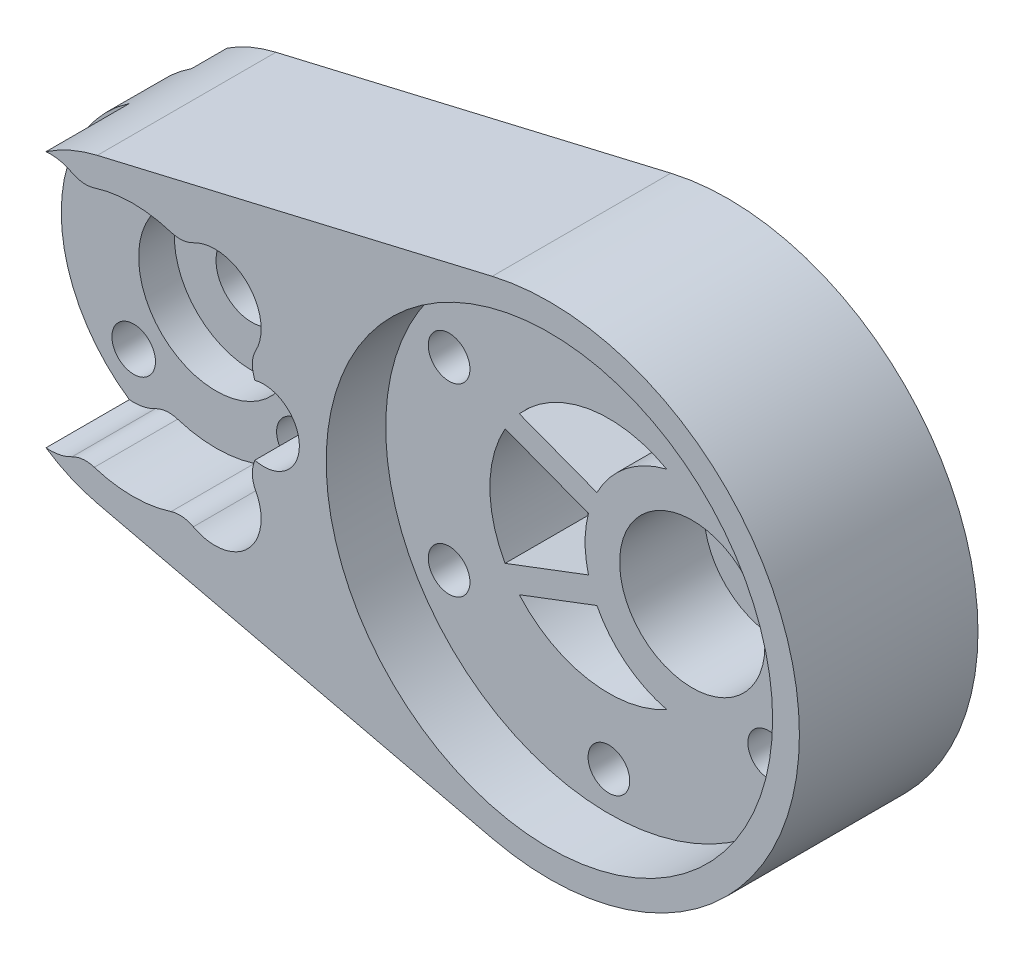
SolidWorks part; units mm, degrees
material "ABS"
ref_plane "Front Plane" through (0, 0, 0) normal (0, 0, 1) x (1, 0, 0)
ref_plane "Top Plane" through (0, 0, 0) normal (0, 1, 0) x (1, 0, 0)
ref_plane "Right Plane" through (0, 0, 0) normal (1, 0, 0) x (0, 0, -1)
sketch "layout" plane through (0, 0, 0) normal (0, 0, 1) x (1, 0, 0)
  line L0 (-87.1613, 0) -> (148.5806, 0) construction
  line L1 (0, 77.4516) -> (0, -79.4839) construction
  line L2 (-2.9714, 12.6559) -> (30.2, 20.4441)
  line L3 (30.2, -20.4441) -> (-2.9714, -12.6559)
  circle A0 centre (0, 0) radius 13
  circle A1 centre (35, 0) radius 21
  circle A3 centre (42, 0) radius 3
  circle A4 centre (11, 0) radius 1.5
  dimension "D1" = 7
  dimension "D2" = 42
  dimension "D3" = 26
  dimension "D4" = 42
  dimension "D5" = 6
  dimension "D6" = 31
  dimension "D7" = 3
sketch "Sketch2" plane through (0, 0, 0) normal (0, 0, 1) x (1, 0, 0)
  line L0 (-2.9714, 12.6559) -> (30.2, 20.4441)
  line L1 (30.2, -20.4441) -> (-2.9714, -12.6559)
  arc A0 (-2.9714, 12.6559) -> (-2.9714, -12.6559) centre (0, 0) ccw
  arc A1 (30.2, -20.4441) -> (30.2, 20.4441) centre (35, 0) ccw
extrude "Boss-Extrude1" add sketch "Sketch2" along normal blind 15
sketch "Sketch5" plane through (0, 0, 15) normal (0, 0, 1) x (1, 0, 0)
  line B0 (2.48, 1.6881) -> (2.48, -1.6881)
  line B1 (-16.002, 0.635) -> (-2.932, 0.635)
  line B2 (-16.002, 4.7625) -> (-16.002, 0.635)
  line B3 (-13.2056, 4.7625) -> (-16.002, 4.7625)
  line B4 (-12.573, -4.7625) -> (-12.573, -4.8306)
  line B5 (-16.002, -4.7625) -> (-12.573, -4.7625)
  line B6 (-16.002, -0.635) -> (-16.002, -4.7625)
  line B7 (-2.932, -0.635) -> (-16.002, -0.635)
  arc B8 (1.3492, -2.6795) -> (2.48, -1.6881) centre (1.48, -1.6881) ccw
  arc B9 (2.48, 1.6881) -> (1.3492, 2.6795) centre (1.48, 1.6881) ccw
  arc B10 (1.3492, 2.6795) -> (-2.932, 0.635) centre (0, 0) ccw
  arc B11 (-13.2056, 4.7625) -> (-10.2587, 7.3504) centre (-13.2056, 7.7343) ccw
  arc B12 (-5.329, 9.8908) -> (-10.2587, 7.3504) centre (-6.9148, 6.9148) ccw
  arc B13 (-5.329, 9.8908) -> (-3.0721, 9.6844) centre (-3.9553, 12.4687) ccw
  arc B14 (3.0721, 9.6844) -> (-3.0721, 9.6844) centre (0, 0) ccw
  arc B15 (3.0721, 9.6844) -> (5.329, 9.8908) centre (3.9553, 12.4687) ccw
  arc B16 (9.8908, 5.329) -> (5.329, 9.8908) centre (6.9148, 6.9148) ccw
  arc B17 (9.8908, 5.329) -> (9.6844, 3.0721) centre (12.4687, 3.9553) ccw
  arc B18 (9.6844, -3.0721) -> (9.6844, 3.0721) centre (0, 0) ccw
  arc B19 (9.6844, -3.0721) -> (9.8908, -5.329) centre (12.4687, -3.9553) ccw
  arc B20 (5.329, -9.8908) -> (9.8908, -5.329) centre (6.9148, -6.9148) ccw
  arc B21 (5.329, -9.8908) -> (3.0721, -9.6844) centre (3.9553, -12.4687) ccw
  arc B22 (-3.0721, -9.6844) -> (3.0721, -9.6844) centre (0, 0) ccw
  arc B23 (-3.0721, -9.6844) -> (-5.329, -9.8908) centre (-3.9553, -12.4687) ccw
  arc B24 (-10.2587, -7.3504) -> (-5.329, -9.8908) centre (-6.9148, -6.9148) ccw
  arc B25 (-10.2587, -7.3504) -> (-12.573, -4.8306) centre (-13.2056, -7.7343) ccw
  arc B26 (-2.932, -0.635) -> (1.3492, -2.6795) centre (0, 0) ccw
sketch_block_instance "Block1-1"
sketch_block "Block1"
sketch "Sketch6" plane through (0, 0, 15) normal (0, 0, 1) x (1, 0, 0)
  line L5 (6.9148, 6.9148) -> (-6.9148, 6.9148) construction
  line L6 (-6.9148, 6.9148) -> (-6.9148, -6.9148) construction
  line L7 (-6.9148, -6.9148) -> (6.9148, -6.9148) construction
  line L8 (6.9148, -6.9148) -> (6.9148, 6.9148) construction
  circle A0 centre (0, 0) radius 3
  circle A2 centre (0, 0) radius 9.779 construction
  circle A3 centre (-6.9148, 6.9148) radius 1.8288
  circle A4 centre (6.9148, 6.9148) radius 1.8288
  circle A5 centre (6.9148, -6.9148) radius 1.8288
  circle A6 centre (-6.9148, -6.9148) radius 1.8288
  dimension "D1" = 3.6576
  dimension "D2" = 19.558
  dimension "D3" = 6
extrude "hub mount hole pattern" cut sketch "Sketch6" against normal through all
sketch "Sketch7" plane through (0, 0, 15) normal (0, 0, 1) x (1, 0, 0)
  line L1 (21.5766, 7.75) -> (21.5766, -7.75) construction
  line L2 (21.5766, -7.75) -> (35, -15.5) construction
  line L3 (35, -15.5) -> (48.4234, -7.75) construction
  line L4 (48.4234, -7.75) -> (48.4234, 7.75) construction
  line L5 (48.4234, 7.75) -> (35, 15.5) construction
  line L6 (35, 15.5) -> (21.5766, 7.75) construction
  circle A0 centre (35, 0) radius 15.5 construction
  circle A1 centre (21.5766, 7.75) radius 1.75
  circle A2 centre (35, 15.5) radius 1.75
  circle A3 centre (48.4234, 7.75) radius 1.75
  circle A4 centre (48.4234, -7.75) radius 1.75
  circle A5 centre (35, -15.5) radius 1.75
  circle A6 centre (21.5766, -7.75) radius 1.75
  circle A7 centre (42, 0) radius 3.25
  dimension "D1" = 3.5
  dimension "D2" = 6.5
  dimension "D3" = 31
extrude "motor hole pattern" cut sketch "Sketch7" against normal through all
sketch "Sketch8" plane through (0, 0, 15) normal (0, 0, 1) x (1, 0, 0)
  circle A0 centre (35, 0) radius 18.75
  dimension "D1" = 37.5
extrude "motor cutout" cut sketch "Sketch8" against normal blind 5
sketch "Sketch9" plane through (0, 0, 15) normal (0, 0, 1) x (1, 0, 0)
  arc A0 (-7.2811, 10.7696) -> (-7.2811, -10.7696) centre (0, 0) ccw
  arc A156 (-10.7546, -7.415) -> (-5.0938, -10.3321) centre (-6.9148, -6.9148) ccw
  arc A157 (-3.2233, -10.161) -> (-5.0938, -10.3321) centre (-3.9553, -12.4687) ccw
  arc A158 (-3.2233, -10.161) -> (3.2233, -10.161) centre (0, 0) ccw
  arc A159 (5.0938, -10.3321) -> (3.2233, -10.161) centre (3.9553, -12.4687) ccw
  arc A160 (10.161, -3.2233) -> (10.3321, -5.0938) centre (12.4687, -3.9553) ccw
  arc A161 (5.0938, -10.3321) -> (10.3321, -5.0938) centre (6.9148, -6.9148) ccw
  arc A162 (10.161, -3.2233) -> (10.161, 3.2233) centre (0, 0) ccw
  arc A163 (10.3321, 5.0938) -> (10.161, 3.2233) centre (12.4687, 3.9553) ccw
  arc A164 (10.3321, 5.0938) -> (5.0938, 10.3321) centre (6.9148, 6.9148) ccw
  arc A165 (3.2233, 10.161) -> (5.0938, 10.3321) centre (3.9553, 12.4687) ccw
  arc A166 (-5.0938, 10.3321) -> (-10.7546, 7.415) centre (-6.9148, 6.9148) ccw
  arc A167 (-5.0938, 10.3321) -> (-3.2233, 10.161) centre (-3.9553, 12.4687) ccw
  arc A168 (3.2233, 10.161) -> (-3.2233, 10.161) centre (0, 0) ccw
  arc A169 (-7.2811, -10.7696) -> (-5.0938, -10.3321) centre (-6.9148, -6.9148) ccw
  arc A170 (-3.2233, -10.161) -> (-5.0938, -10.3321) centre (-3.9553, -12.4687) ccw
  arc A171 (-3.2233, -10.161) -> (3.2233, -10.161) centre (0, 0) ccw
  arc A172 (5.0938, -10.3321) -> (3.2233, -10.161) centre (3.9553, -12.4687) ccw
  arc A173 (10.161, -3.2233) -> (10.3321, -5.0938) centre (12.4687, -3.9553) ccw
  arc A174 (5.0938, -10.3321) -> (10.3321, -5.0938) centre (6.9148, -6.9148) ccw
  arc A175 (10.161, -3.2233) -> (10.161, 3.2233) centre (0, 0) ccw
  arc A176 (10.3321, 5.0938) -> (10.161, 3.2233) centre (12.4687, 3.9553) ccw
  arc A177 (10.3321, 5.0938) -> (5.0938, 10.3321) centre (6.9148, 6.9148) ccw
  arc A178 (3.2233, 10.161) -> (5.0938, 10.3321) centre (3.9553, 12.4687) ccw
  arc A179 (-5.0938, 10.3321) -> (-7.2811, 10.7696) centre (-6.9148, 6.9148) ccw
  arc A180 (-5.0938, 10.3321) -> (-3.2233, 10.161) centre (-3.9553, 12.4687) ccw
  arc A181 (3.2233, 10.161) -> (-3.2233, 10.161) centre (0, 0) ccw
  dimension "D1" = 0.5
extrude "hub mount cutout" cut sketch "Sketch9" against normal blind 7
sketch "Sketch10" plane through (0, 0, 0) normal (0, 0, -1) x (-1, 0, 0)
  circle A0 centre (-11, 0) radius 5
  dimension "D1" = 10
extrude "Boss-Extrude2" add sketch "Sketch10" along normal blind 5.5
sketch "Sketch12" plane through (0, 0, 0) normal (0, 0, 1) x (1, 0, 0)
  circle A0 centre (11, 0) radius 1.55
  dimension "D1" = 3.1
extrude "Linkage pin hole" cut sketch "Sketch12" against normal through all both and the other way through all
chamfer "Chamfer1" distance 2.75 angle 45 1 edges at (6, 0, -5.5)
sketch "Sketch13" plane through (0, 0, 10) normal (0, 0, 1) x (1, 0, 0)
  circle A0 centre (42, 0) radius 6.1
  dimension "D1" = 12.2
extrude "Cut-Extrude7" cut sketch "Sketch13" against normal blind 7.1
sketch "Sketch14" plane through (0, 0, 8) normal (0, 0, 1) x (1, 0, 0)
  circle A0 centre (0, 0) radius 6.5
  dimension "D1" = 13
extrude "Cut-Extrude8" cut sketch "Sketch14" against normal blind 3
sketch "Sketch15" plane through (0, 0, 0) normal (0, 0, -1) x (-1, 0, 0)
  circle A0 centre (-21.5766, -7.75) radius 3.5
  circle A1 centre (-35, -15.5) radius 3.5
  circle A2 centre (-48.4234, -7.75) radius 3.5
  circle A3 centre (-48.4234, 7.75) radius 3.5
  circle A4 centre (-35, 15.5) radius 3.5
  circle A5 centre (-21.5766, 7.75) radius 3.5
  dimension "D1" = 7
extrude "Cut-Extrude9" cut sketch "Sketch15" against normal offset from surface (5 mm away) 5 up to face at (48.1, 0, 10)
sketch "Sketch16" plane through (0, 0, 8) normal (0, 0, 1) x (1, 0, 0)
  circle A0 centre (11, 0) radius 3
  dimension "D1" = 6
extrude "Cut-Extrude10" cut sketch "Sketch16" against normal offset from surface 10.5 and the other way through all up to face at (8.75, 0, -5.5)
sketch "Sketch17" plane through (0, 0, 10) normal (0, 0, 1) x (1, 0, 0)
  arc A0 (39.8571, 8.7412) -> (39.8571, -8.7412) centre (35, 0) ccw
  arc A1 (39.8571, 8.7412) -> (39.8571, -8.7412) centre (42, 0) ccw
  dimension "D1" = 9
  dimension "D2" = 10
extrude "Cut-Extrude12" cut sketch "Sketch17" against normal offset from surface (7 mm away) 3 up to face at (18.0766, 7.75, 0)
sketch "Sketch18" plane through (0, 0, 10) normal (0, 0, 1) x (1, 0, 0)
  line L0 (21.5766, -7.75) -> (42, 0) construction
  line L1 (21.5766, 7.75) -> (42, 0) construction
  line L2 (27.472, -6.5825) -> (33.9923, -4.1082)
  line L3 (27.472, 6.5825) -> (33.9923, 4.1082)
  line L4 (26.2803, -4.8955) -> (33.2828, -2.2383)
  line L5 (26.2803, 4.8955) -> (33.2828, 2.2383)
  line L6 (21.9314, -8.6849) -> (44.8186, 0) construction
  line L7 (21.2218, -6.8151) -> (39.1814, 0) construction
  line L8 (21.9314, 8.6849) -> (44.8186, 0) construction
  line L9 (21.2218, 6.8151) -> (39.1814, 0) construction
  arc A0 (39.8571, 8.7412) -> (39.8571, -8.7412) centre (35, 0) ccw construction
  arc A1 (39.8571, 8.7412) -> (39.8571, -8.7412) centre (42, 0) ccw construction
  arc A2 (27.472, 6.5825) -> (26.2803, 4.8955) centre (35, 0) ccw
  arc A3 (33.9923, 4.1082) -> (33.2828, 2.2383) centre (42, 0) ccw
  arc A5 (26.2803, -4.8955) -> (27.472, -6.5825) centre (35, 0) ccw
  arc A6 (33.2828, -2.2383) -> (33.9923, -4.1082) centre (42, 0) ccw
  dimension "D1" = 1
  dimension "D2" = 1
extrude "Boss-Extrude3" add sketch "Sketch18" against normal up to next
sketch "Sketch19" plane through (0, 0, 0) normal (0, 0, -1) x (-1, 0, 0)
  circle A0 centre (-6.9148, -6.9148) radius 4
  circle A1 centre (-6.9148, 6.9148) radius 4
  circle A2 centre (6.9148, 6.9148) radius 4
  circle A3 centre (6.9148, -6.9148) radius 4
  dimension "D1" = 8
extrude "Cut-Extrude13" cut sketch "Sketch19" against normal offset from surface 5 and the other way through all up to face at (2.6581, 0, 8)
fillet "Fillet1" radius 5 2 edges at (16, 0, 0) (6, 0, 0)
